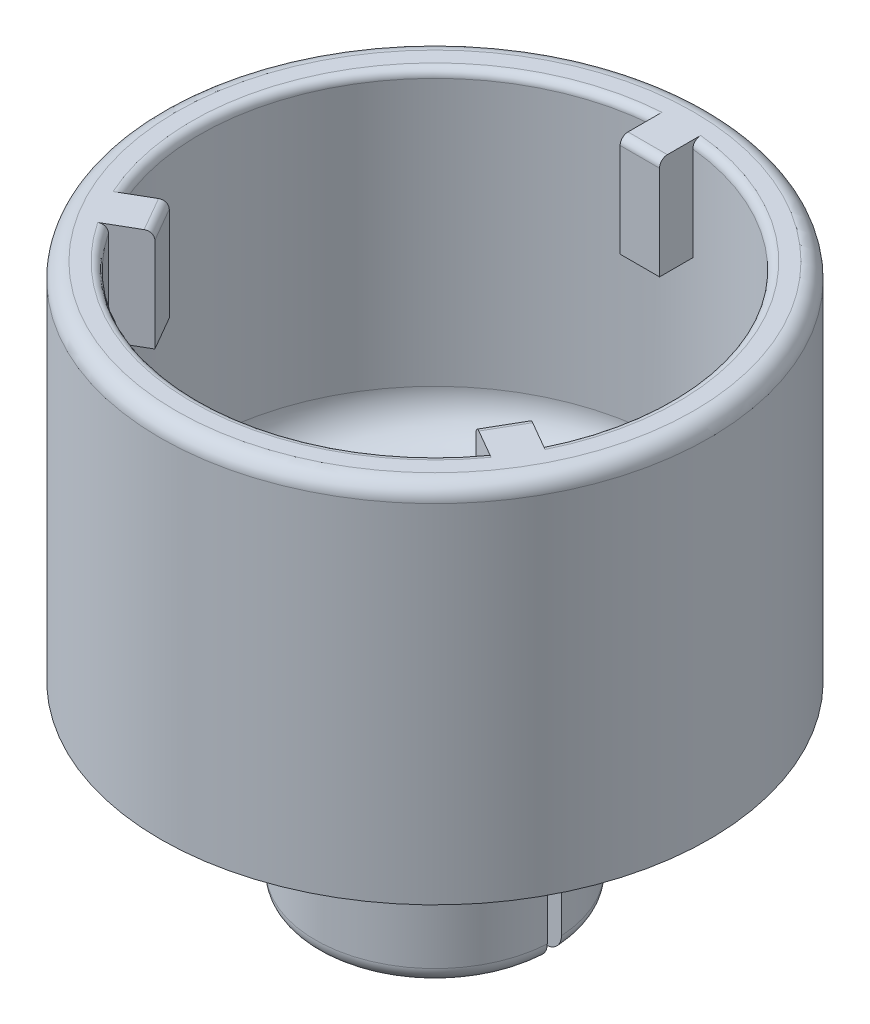
SolidWorks part; units mm, degrees
ref_plane "Front Plane" through (0, 0, 0) normal (0, 0, 1) x (1, 0, 0)
ref_plane "Top Plane" through (0, 0, 0) normal (0, 1, 0) x (1, 0, 0)
ref_plane "Right Plane" through (0, 0, 0) normal (1, 0, 0) x (0, 0, -1)
sketch "Sketch1" plane through (0, 0, 0) normal (0, 1, 0) x (1, 0, 0)
  circle A0 centre (0, 0) radius 35
  dimension "D1" = 70
extrude "Boss-Extrude1" add sketch "Sketch1" along normal blind 46.3
sketch "Sketch2" plane through (0, 46.3, 0) normal (0, 1, 0) x (1, 0, 0)
  circle A0 centre (0, 0) radius 30
  dimension "D1" = 60
extrude "Cut-Extrude1" cut sketch "Sketch2" against normal blind 40
sketch "Sketch3" plane through (0, 0, 0) normal (0, -1, 0) x (1, 0, 0)
  circle A0 centre (0, 0) radius 19.5
  dimension "D1" = 39
extrude "Boss-Extrude2" add sketch "Sketch3" along normal blind 7
sketch "Sketch4" plane through (0, -7, 0) normal (0, -1, 0) x (1, 0, 0)
  circle A0 centre (0, 0) radius 15.25
  dimension "D1" = 30.5
extrude "Boss-Extrude3" add sketch "Sketch4" along normal blind 16
fillet "Fillet1" radius 5 1 edges at (0, 0, -19.5)
sketch "Sketch5" plane through (0, 46.3, 0) normal (0, 1, 0) x (1, 0, 0)
  line L0 (-1.9905, 29.9339) -> (-1.9905, 25.6053)
  line L1 (-1.9905, 25.6053) -> (3.0302, 25.6053)
  line L2 (3.0302, 25.6053) -> (3.0302, 29.8466)
  line L3 (26.9188, -13.2431) -> (23.1701, -11.0788)
  line L4 (23.1701, -11.0788) -> (20.6597, -15.4269)
  line L5 (20.6597, -15.4269) -> (24.3328, -17.5475)
  line L6 (-24.9282, -16.6908) -> (-21.1796, -14.5265)
  line L7 (-21.1796, -14.5265) -> (-23.69, -10.1784)
  line L8 (-23.69, -10.1784) -> (-27.363, -12.299)
  circle A0 centre (0, 0) radius 30 construction
  arc A1 (24.3328, -17.5475) -> (26.9188, -13.2431) centre (0, 0) ccw
  circle A2 centre (0, 0) radius 30
  arc A3 (3.0302, 29.8466) -> (-1.9905, 29.9339) centre (0, 0) ccw
  arc A4 (-27.363, -12.299) -> (-24.9282, -16.6908) centre (0, 0) ccw
  point P19 (0, 0)
  dimension "D1" = 0
  dimension "D2" = 3
extrude "Boss-Extrude4" add sketch "Sketch5" against normal blind 13
sketch "Sketch7" plane through (0, -23, 0) normal (0, -1, 0) x (1, 0, 0)
  line L1 (33.0968, 0.9034) -> (-33.0968, 0.9034)
  line L2 (33.0968, 0.9034) -> (33.0968, -0.9034)
  line L3 (33.0968, -0.9034) -> (-33.0968, -0.9034)
  line L4 (-33.0968, 0.9034) -> (-33.0968, -0.9034)
  line L5 (33.0968, 0.9034) -> (-33.0968, -0.9034) construction
  line L6 (33.0968, -0.9034) -> (-33.0968, 0.9034) construction
  point P0 (0, 0)
extrude "Cut-Extrude2" cut sketch "Sketch7" against normal up to surface (16 mm away) up to face at (0, -7, -15.25)
fillet "Fillet2" radius 2 2 edges at (0, -23, 15.25) (0, -23, -15.25)
sketch "Sketch8" plane through (0, 6.3, 0) normal (0, 1, 0) x (1, 0, 0)
  circle A0 centre (0, 0) radius 10.3601
fillet "Fillet3" radius 5 1 edges at (0, 6.3, 30)
fillet "Fillet4" radius 2 1 edges at (0, 46.3, 35)
fillet "Fillet5" radius 1 3 edges at (-0.5217, 46.3, 29.9955) (26.2377, 46.3, -14.5459) (-25.716, 46.3, -15.4495)
fillet "Fillet6" radius 1 3 edges at (21.9149, 46.3, 13.2529) (-22.4348, 46.3, 12.3525) (0.5198, 46.3, -25.6053)
